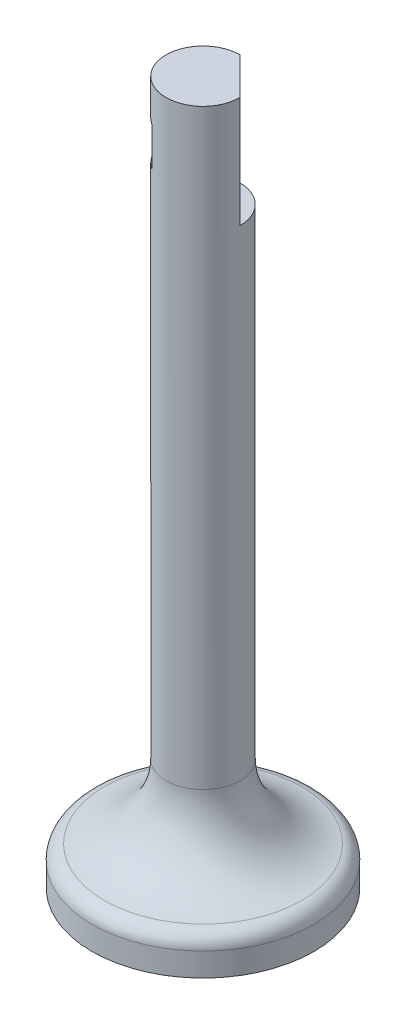
SolidWorks part; units mm, degrees
ref_plane "Спереди" through (0, 0, 0) normal (0, 0, 1) x (1, 0, 0)
ref_plane "Сверху" through (0, 0, 0) normal (0, 1, 0) x (1, 0, 0)
ref_plane "Справа" through (0, 0, 0) normal (1, 0, 0) x (0, 0, -1)
sketch "Sketch1" plane through (0, 0, 0) normal (0, 1, 0) x (1, 0, 0)
  circle A0 centre (0, 0) radius 15
  dimension "D1" = 30
extrude "Boss-Extrude1" add sketch "Sketch1" along normal blind 5
sketch "Sketch2" plane through (0, 5, 0) normal (0, 1, 0) x (1, 0, 0)
  circle A0 centre (0, 0) radius 5
  dimension "D1" = 10
extrude "Boss-Extrude2" add sketch "Sketch2" along normal blind 90
sketch "Sketch3" plane through (0, 95, 0) normal (0, 1, 0) x (1, 0, 0)
  line L0 (0, 5) -> (5, 0)
  circle A0 centre (0, 0) radius 5 construction
  arc A1 (0, 5) -> (5, 0) centre (0, 0) cw
extrude "Cut-Extrude1" cut sketch "Sketch3" against normal blind 15
sketch "Sketch4" plane through (2.5, 0, -2.5) normal (0.7071, 0, -0.7071) x (-0.7071, 0, -0.7071)
  line L0 (0, 95) -> (0, 80) construction
  line L1 (3.5355, 95) -> (-3.5355, 95) construction
  line L2 (3.5355, 80) -> (-3.5355, 80) construction
  line L4 (1, 90.1) -> (-1, 90.1)
  line L5 (1, 90.1) -> (1, 84.9)
  line L6 (1, 84.9) -> (-1, 84.9)
  line L7 (-1, 90.1) -> (-1, 84.9)
  line L8 (1, 90.1) -> (-1, 84.9) construction
  line L9 (1, 84.9) -> (-1, 90.1) construction
  point P6 (0, 87.5)
  dimension "D1" = 5.2
  dimension "D2" = 2
extrude "Cut-Extrude2" cut sketch "Sketch4" against normal through all
fillet "Fillet1" radius 10 1 edges at (0, 5, 5)
fillet "Fillet2" radius 2 1 edges at (0, 5, 15)
sketch "Sketch5" plane through (0, 0, 0) normal (0, -1, 0) x (1, 0, 0)
  line L0 (10.6066, -10.6066) -> (-10.6066, 10.6066) construction
  line L1 (2.1213, 14.8492) -> (-14.8492, -2.1213) construction
  line L2 (0, -5) -> (5, 0) construction
  circle A0 centre (0, 0) radius 15 construction
  text T0 "T" font "Arial" height 16
  point P2 (-6.364, 6.364)
  dimension "D1" = 6
extrude "Cut-Extrude3" cut sketch "Sketch5" against normal blind 1
sketch "Sketch6" plane through (0, 0, 0) normal (0, -1, 0) x (1, 0, 0)
  circle A0 centre (0, 0) radius 11.5
  circle A1 centre (0, 0) radius 13.5
  dimension "D1" = 2
  dimension "D2" = 27
extrude "Cut-Extrude4" cut sketch "Sketch6" against normal blind 1
